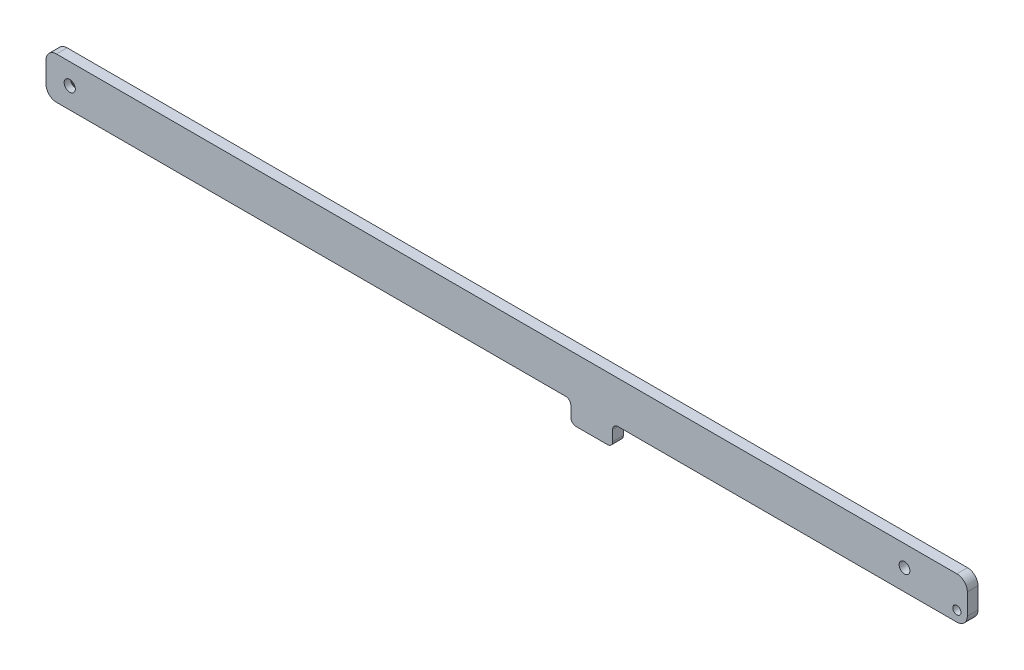
SolidWorks part; units mm, degrees
material "PC High Viscosity"
ref_plane "Front Plane" through (0, 0, 0) normal (0, 0, 1) x (1, 0, 0)
ref_plane "Top Plane" through (0, 0, 0) normal (0, 1, 0) x (1, 0, 0)
ref_plane "Right Plane" through (0, 0, 0) normal (1, 0, 0) x (0, 0, -1)
sketch "Sketch1" plane through (0, 0, 0) normal (0, 0, 1) x (1, 0, 0)
  line L1 (0, 0) -> (40.5308, 0)
  line L2 (0, 0) -> (0, 25.4)
  line L3 (0, 25.4) -> (40.5307, 25.4)
  line L4 (558.8, 0) -> (558.8, 25.4)
  line L11 (558.8, 10.0162) -> (552.45, 13.6823) construction
  line L12 (552.45, 13.6823) -> (546.1, 10.0162) construction
  line L13 (546.1, 10.0162) -> (546.1, 2.6838) construction
  line L14 (546.1, 2.6838) -> (552.45, -0.9823) construction
  line L15 (552.45, -0.9823) -> (558.8, 2.6838) construction
  line L16 (558.8, 2.6838) -> (558.8, 10.0162) construction
  line L19 (318.3103, 0) -> (318.3103, -12.7)
  line L20 (318.3103, -12.7) -> (343.7103, -12.7)
  line L21 (343.7103, -12.7) -> (343.7103, 0)
  line L22 (40.5307, 25.4) -> (558.8, 25.4)
  line L23 (40.5308, 0) -> (318.3103, 0)
  line L24 (343.7103, 0) -> (558.8, 0)
  circle A0 centre (552.45, 6.35) radius 2.4892
  circle A1 centre (552.45, 6.35) radius 6.35 construction
  dimension "D5" = 4.9784
  dimension "D7" = 12.7
  dimension "D1" = 558.8
  dimension "D2" = 25.4
  dimension "D3" = 12.7
  dimension "D4" = 318.3103
  dimension "D9" = 25.4
extrude "Boss-Extrude1" add sketch "Sketch1" along normal blind 6.477 contours L3 | L1 L4 L3 L2 A0 | L1 region at (280.1818, 12.2846, 0)
fillet "Fillet2" radius 6.35 4 edges at (558.8, 25.4, 3.2385) (0, 0, 3.2385) (0, 25.4, 3.2385) (558.8, 0, 3.2385)
sketch "Sketch2" plane through (0, 0, 6.477) normal (0, 0, 1) x (1, 0, 0)
  line L2 (558.8, 6.35) -> (558.8, 19.05) construction
  line L3 (6.35, 25.4) -> (552.45, 25.4) construction
  circle A0 centre (520.7, 12.7) radius 3.2639
  dimension "D1" = 6.5278
  dimension "D2" = 12.7
  dimension "D3" = 38.1
mirror "Mirror2" about plane through (0, 0, 0) normal (0, 0, 1) of bodies 101 108
delete or keep bodies "Body-Delete/Keep 1" type delete bodies bodies 101
fillet "Fillet3" radius 3.175 4 edges at (343.7103, 0, -3.2385) (343.7103, -12.7, -3.2385) (318.3103, -12.7, -3.2385) (318.3103, 0, -3.2385)
extrude "Cut-Extrude1" cut sketch "Sketch2" against normal through all
hole_wizard "CSK for 1/4 Flat Head Machine Screw (100)1" positions "Sketch3" profile "Sketch4" countersink size "1/4" standard "ANSI Inch"
sketch "Sketch3" plane through (0, 0, -6.477) normal (0, 0, 1) x (1, 0, 0)
  line L0 (6.35, 0) -> (315.1353, 0) construction
  line L1 (0, 6.35) -> (0, 19.05) construction
  point P0 (14.3939, 12.7)
  dimension "D1" = 12.7
  dimension "D2" = 14.3939
sketch "Sketch4" plane through (14.3939, 12.7, -6.477) normal (1, 0, 0) x (0, 1, 0)
  line L0 (0, 0) -> (0, 21.0798)
  line L1 (0, 21.0798) -> (3.3782, 19.05)
  line L2 (3.3782, 19.05) -> (3.3782, 2.5682)
  line L3 (3.3782, 2.5682) -> (6.4389, 0)
  line L5 (6.4389, 0) -> (0, 0)
  line L6 (-3.3782, 2.5682) -> (-6.4389, 0) construction
  line L10 (0, 21.0798) -> (-3.3782, 19.05) construction
  line L11 (0, -6.35) -> (0, 107.95) construction
  dimension "Hole Dia." = 6.7564
  dimension "Hole Depth" = 19.05
  dimension "Near C'Sink Dia." = 12.8778
  dimension "Near C'Sink Angle" = 100
  dimension "Drill Angle" = 118
